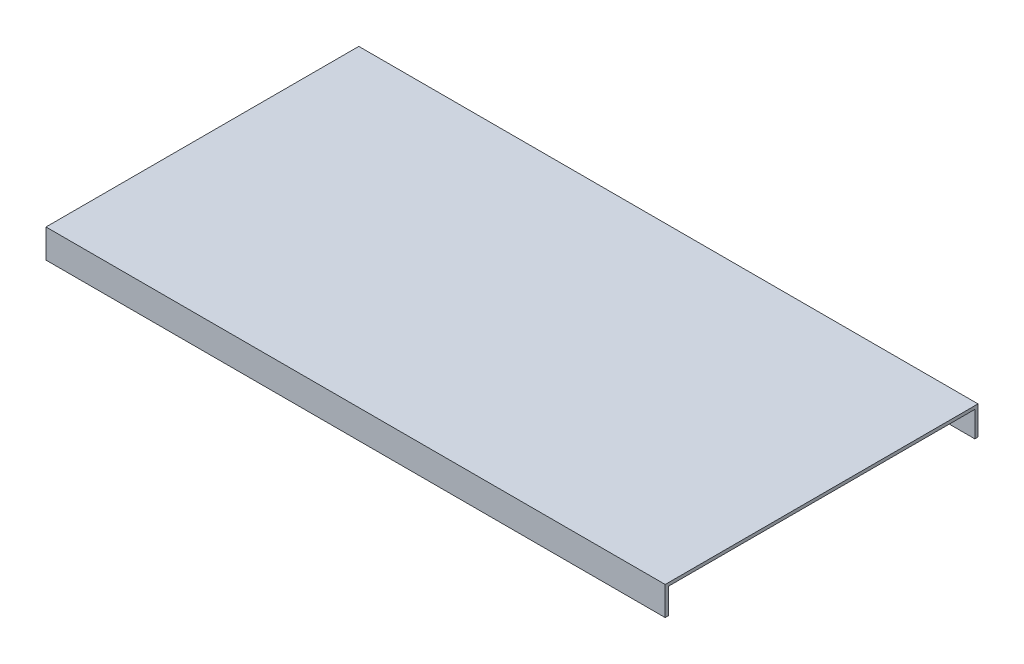
SolidWorks part; units mm, degrees
material "ASTM A36 Steel"
ref_plane "Front Plane" through (0, 0, 0) normal (0, 0, 1) x (1, 0, 0)
ref_plane "Top Plane" through (0, 0, 0) normal (0, 1, 0) x (1, 0, 0)
ref_plane "Right Plane" through (0, 0, 0) normal (1, 0, 0) x (0, 0, -1)
sketch "Sketch1" plane through (0, 0, 0) normal (0, 1, 0) x (1, 0, 0)
  line L1 (153.9875, 77.7875) -> (-153.9875, 77.7875)
  line L2 (153.9875, 77.7875) -> (153.9875, -77.7875)
  line L3 (153.9875, -77.7875) -> (-153.9875, -77.7875)
  line L4 (-153.9875, 77.7875) -> (-153.9875, -77.7875)
  line L5 (153.9875, 77.7875) -> (-153.9875, -77.7875) construction
  line L6 (153.9875, -77.7875) -> (-153.9875, 77.7875) construction
  point P0 (0, 0)
  dimension "D1" = 307.975
  dimension "D2" = 155.575
extrude "Boss-Extrude1" add sketch "Sketch1" along normal blind 1.5875
sketch "Sketch2" plane through (0, 0, 0) normal (0, -1, 0) x (1, 0, 0)
  line L4 (152.4, 76.2) -> (153.9875, 76.2)
  line L5 (152.4, -76.2) -> (153.9875, -76.2)
  line L8 (-152.4, 76.2) -> (-152.4, -76.2)
  line L9 (-152.4, -76.2) -> (152.4, -76.2)
  line L10 (152.4, -76.2) -> (152.4, 76.2)
  line L11 (152.4, 76.2) -> (-152.4, 76.2)
  line L12 (-152.4, 76.2) -> (-152.4, -76.2)
  line L13 (-152.4, -76.2) -> (152.4, -76.2)
  line L14 (152.4, -76.2) -> (152.4, 76.2)
  line L15 (152.4, 76.2) -> (-152.4, 76.2)
  line L16 (-153.9875, 77.7875) -> (-153.9875, -77.7875)
  line L17 (-153.9875, -77.7875) -> (153.9875, -77.7875)
  line L18 (153.9875, -77.7875) -> (153.9875, 77.7875)
  line L19 (153.9875, 77.7875) -> (-153.9875, 77.7875)
  line L20 (-153.9875, 77.7875) -> (-153.9875, -77.7875)
  line L21 (-153.9875, -77.7875) -> (153.9875, -77.7875)
  line L22 (153.9875, -77.7875) -> (153.9875, 77.7875)
  line L23 (153.9875, 77.7875) -> (-153.9875, 77.7875)
  line M9 (-153.9875, 77.7875) -> (-153.9875, -77.7875)
  line M10 (-153.9875, -77.7875) -> (153.9875, -77.7875)
  line M11 (153.9875, -77.7875) -> (153.9875, 77.7875)
  line M12 (153.9875, 77.7875) -> (-153.9875, 77.7875)
  dimension "D1" = 1.5875
  dimension "D2" = 0
extrude "Boss-Extrude2" add sketch "Sketch2" along normal blind 12.7 contours L15 L4 L5 L13 L12 M11 M12 M9 M10 region at (0, 0, 76.545)
